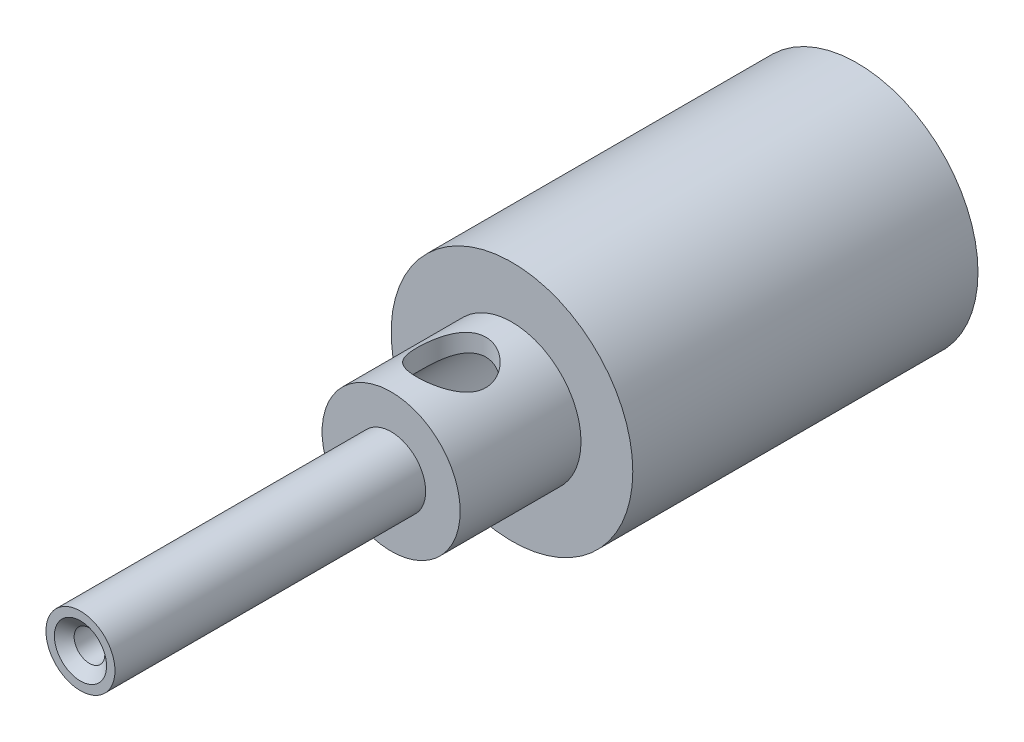
SolidWorks part; units mm, degrees
material "AISI 1020"
ref_plane "Front" through (0, 0, 0) normal (0, 0, 1) x (1, 0, 0)
ref_plane "Top" through (0, 0, 0) normal (0, 1, 0) x (1, 0, 0)
ref_plane "Right" through (0, 0, 0) normal (1, 0, 0) x (0, 0, -1)
sketch "Sketch1" plane through (0, 0, 0) normal (0, 0, 1) x (1, 0, 0)
  circle A0 centre (0, 0) radius 7
extrude "Boss-Extrude1" add sketch "Sketch1" along normal blind 20
sketch "Sketch2" plane through (0, 0, 20) normal (0, 0, 1) x (1, 0, 0)
  circle A0 centre (0, 0) radius 4
extrude "Boss-Extrude2" add sketch "Sketch2" along normal blind 7
sketch "Sketch3" plane through (0, 0, 27) normal (0, 0, 1) x (1, 0, 0)
  circle A0 centre (0, 0) radius 2
extrude "Boss-Extrude3" add sketch "Sketch3" along normal blind 18
sketch "Sketch6" plane through (0, 0, 0) normal (0, 1, 0) x (1, 0, 0)
  circle A0 centre (0, -23.5116) radius 2
extrude "Cut-Extrude3" cut sketch "Sketch6" against normal blind 32 and the other way blind 32
hole_wizard "CSK for #0 Flat Head Machine Screw (100)1" positions "Sketch8" profile "Sketch9" countersink size "#0" standard "ANSI Inch" end condition up to next
sketch "Sketch8" plane through (0, 0, 45) normal (0, 0, 1) x (1, 0, 0)
  point P0 (0, 0)
sketch "Sketch9" plane through (0, 0, 45) normal (1, 0, 0) x (0, -1, 0)
  line L0 (0, 0) -> (0, 19.4884)
  line L1 (0, 19.4884) -> (0.889, 19.4884)
  line L2 (0.889, 19.4884) -> (0.889, 0.5222)
  line L3 (0.889, 0.5222) -> (1.5113, 0)
  line L5 (1.5113, 0) -> (0, 0)
  line L6 (-0.889, 0.5222) -> (-1.5113, 0) construction
  line L11 (0, -6.35) -> (0, 107.95) construction
  dimension "Thru Hole Dia." = 1.778
  dimension "Thru Hole Depth" = 19.4884
  dimension "Near C'Sink Dia." = 3.0226
  dimension "Near C'Sink Angle" = 100
sketch "Sketch12" plane through (0, 0, 0) normal (0, 0, -1) x (-1, 0, 0)
  circle A0 centre (0, 0) radius 4
extrude "Boss-Extrude4" add sketch "Sketch12" along normal blind 1
sketch "Sketch4" plane through (0, 0, 0) normal (0, 0, -1) x (-1, 0, 0)
  circle A0 centre (0, 0) radius 3
extrude "Cut-Extrude5" cut sketch "Sketch4" against normal blind 26.8849 and the other way blind 8 contours A0
